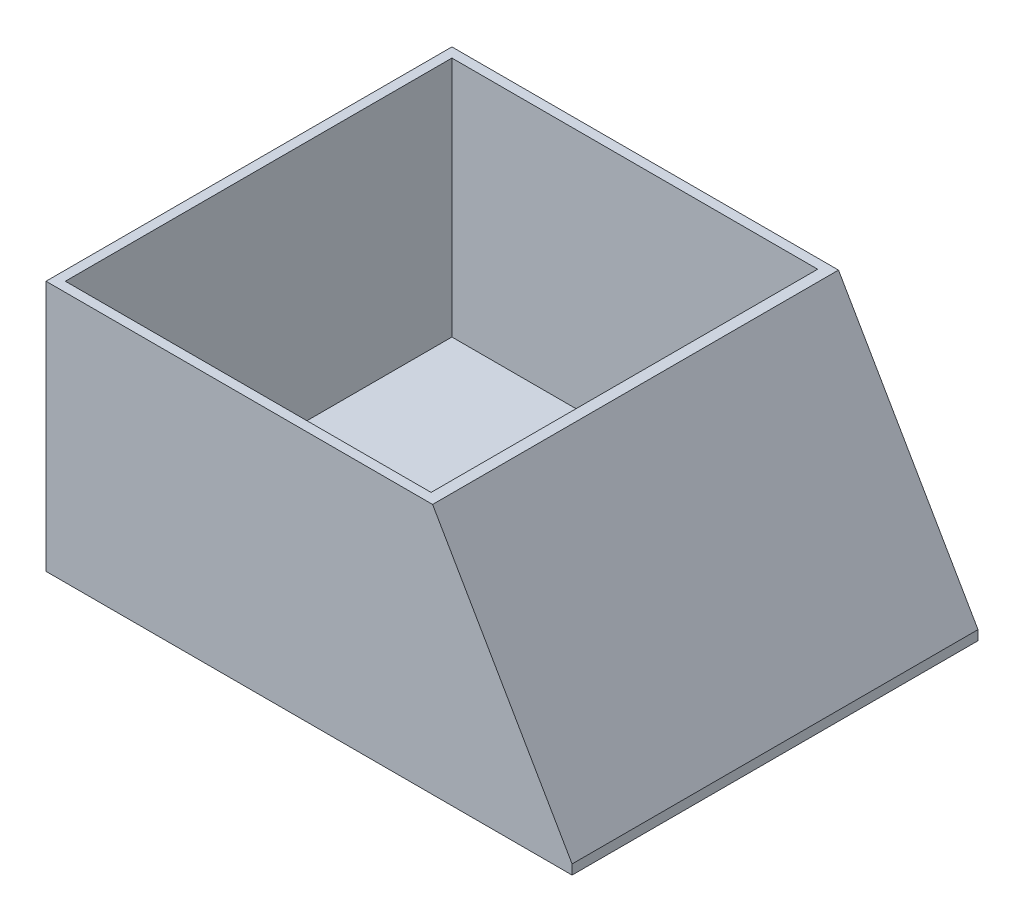
SolidWorks part; units mm, degrees
ref_plane "Front Plane" through (0, 0, 0) normal (0, 0, 1) x (1, 0, 0)
ref_plane "Top Plane" through (0, 0, 0) normal (0, 1, 0) x (1, 0, 0)
ref_plane "Right Plane" through (0, 0, 0) normal (1, 0, 0) x (0, 0, -1)
sketch "Sketch2" plane through (0, 0, 0) normal (0, 0, 1) x (1, 0, 0)
  line L0 (160.3013, 0) -> (-3, 0)
  line L1 (-3, 0) -> (-3, 75)
  line L2 (-3, 75) -> (117, 75)
  line L3 (117, 75) -> (160.3013, 0)
  line L4 (0, 75) -> (0, 0)
  line L5 (113.5359, 75) -> (156.8372, 0)
  line L6 (-3, 37.5) -> (0, 37.5) construction
  line L7 (135.1865, 37.5) -> (137.7846, 39) construction
  line L8 (-3, 0) -> (-3, -3)
  line L9 (-3, -3) -> (160.3013, -3)
  line L10 (160.3013, -3) -> (160.3013, 0)
  dimension "D1" = 3
  dimension "D2" = 120
  dimension "D3" = 75
  dimension "D4" = 90
  dimension "D5" = 60
ref_plane "Plane1" through (0, 0, 60) normal (0, 0, 1) x (1, 0, 0)
extrude "Boss-Extrude3" add sketch "Sketch2" along normal up to surface (60 mm away) contours L4 L2 L1 L0 | L2 L5 L0 L3 | L9 L10 L0 L8 region at (78.6506, -1.5, 0) region at (136.9186, 37.5, 0) region at (-1.5, 37.5, 0) up to plane "Plane1"
extrude "Boss-Extrude4" add sketch "Sketch2<3>" along normal blind 3 from surface contours L2 L5 L0 L3 | L9 L10 L0 L8 | L5 L2 L4 L0 | L4 L2 L1 L0 region at (78.6506, -1.5, 0) region at (136.9186, 37.5, 0) region at (68.1712, 35.4981, 0) region at (-1.5, 37.5, 0) starting at plane "Plane1"
sketch "Sketch2<3>" plane through (0, 0, 0) normal (0, 0, 1) x (1, 0, 0) same geometry as "Sketch2"
mirror "Mirror2" about plane through (0, 0, 0) normal (0, 0, 1) of bodies 109
